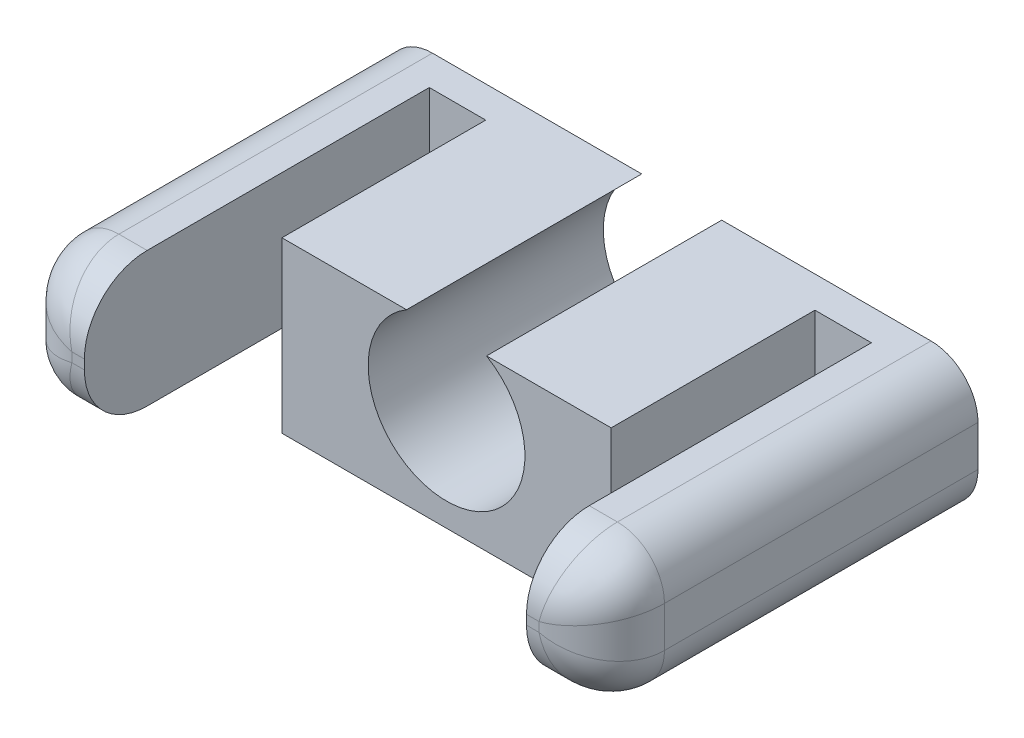
SolidWorks part; units mm, degrees
material "ABS PC"
ref_plane "Front Plane" through (0, 0, 0) normal (0, 0, 1) x (1, 0, 0)
ref_plane "Top Plane" through (0, 0, 0) normal (0, 1, 0) x (1, 0, 0)
ref_plane "Right Plane" through (0, 0, 0) normal (1, 0, 0) x (0, 0, -1)
sketch "Sketch1" plane through (0, 0, 0) normal (0, 0, 1) x (1, 0, 0)
  line L0 (-5.25, 3.25) -> (-7.0483, 3.25)
  line L1 (5.25, -3.25) -> (-5.25, -3.25)
  line L2 (5.25, -3.25) -> (5.25, 3.25)
  line L3 (5.25, 3.25) -> (-5.25, 3.25)
  line L4 (-5.25, -3.25) -> (-5.25, 3.25)
  line L5 (5.25, -3.25) -> (-5.25, 3.25) construction
  line L6 (5.25, 3.25) -> (-5.25, -3.25) construction
  circle A0 centre (0, 0) radius 2.5
  point P0 (0, 0)
  dimension "D3" = 5
  dimension "D1" = 10.5
  dimension "D2" = 6.5
extrude "Boss-Extrude1" add sketch "Sketch1" along normal blind 7.5 contours L4 L1 L2 L3 A0 region at (0, -3.1265, 0)
sketch "Sketch2" plane through (0, 0, 0) normal (0, 0, -1) x (-1, 0, 0)
  line L0 (-6.9062, 0) -> (7.5938, 0) construction
  line L1 (5.25, 2.15) -> (7.95, 2.15)
  line L2 (5.25, -3.25) -> (5.25, 3.25) construction
  line L3 (9.45, 0.65) -> (9.45, -0.65)
  line L4 (7.95, -2.15) -> (5.25, -2.15)
  line L5 (5.25, -2.15) -> (5.25, 2.15)
  line L6 (0, 55) -> (0, -55) construction
  line L7 (-7.95, -2.15) -> (-5.25, -2.15)
  line L8 (-9.45, 0.65) -> (-9.45, -0.65)
  line L9 (-5.25, 2.15) -> (-7.95, 2.15)
  line L10 (-5.25, -2.15) -> (-5.25, 2.15)
  arc A0 (7.95, -2.15) -> (9.45, -0.65) centre (7.95, -0.65) ccw
  arc A1 (7.95, 2.15) -> (9.45, 0.65) centre (7.95, 0.65) cw
  arc A2 (-7.95, -2.15) -> (-9.45, -0.65) centre (-7.95, -0.65) cw
  arc A3 (-7.95, 2.15) -> (-9.45, 0.65) centre (-7.95, 0.65) ccw
  point P11 (9.45, -2.15)
  point P14 (9.45, 2.15)
  dimension "D4" = 1.5
  dimension "D1" = 4.2
  dimension "D2" = 4.3
  dimension "D3" = 2.15
extrude "Boss-Extrude2" add sketch "Sketch2" against normal blind 12
sketch "Sketch4" plane through (0, 0, 12) normal (0, 0, 1) x (1, 0, 0)
  line L0 (-5.25, -2.15) -> (-7.95, -2.15) construction
  line L1 (-5.25, 2.15) -> (-7.05, 2.15)
  line L2 (-5.25, 2.15) -> (-5.25, -2.15)
  line L3 (-5.25, -2.15) -> (-7.05, -2.15)
  line L4 (-7.05, 2.15) -> (-7.05, -2.15)
  line L5 (7.95, -2.15) -> (5.25, -2.15) construction
  line L6 (5.25, 2.15) -> (7.05, 2.15)
  line L7 (5.25, 2.15) -> (5.25, -2.15)
  line L8 (5.25, -2.15) -> (7.05, -2.15)
  line L9 (7.05, 2.15) -> (7.05, -2.15)
  dimension "D1" = 1.8
  dimension "D2" = 1.8
extrude "Cut-Extrude1" cut sketch "Sketch4" against normal blind 11
fillet "Fillet2" radius 2 10 edges at (-7.5, -2.15, 12) (-9.0107, -1.7107, 12) (-9.45, 0, 12) (-7.5, 2.15, 12) (7.5, 2.15, 12) (7.5, -2.15, 12) (9.0107, -1.7107, 12) (9.45, 0, 12) (-9.0107, 1.7107, 12) (9.0107, 1.7107, 12)
sketch "Sketch5" plane through (0, 0, 0) normal (0, 0, -1) x (-1, 0, 0)
  line L0 (-5.25, 3.25) -> (5.25, 3.25)
  line L1 (5.25, 3.25) -> (5.25, 2.15)
  line L2 (5.25, 2.15) -> (-5.25, 2.15)
  line L3 (-5.25, 2.15) -> (-5.25, 3.25)
extrude "Cut-Extrude2" cut sketch "Sketch5" against normal through all
